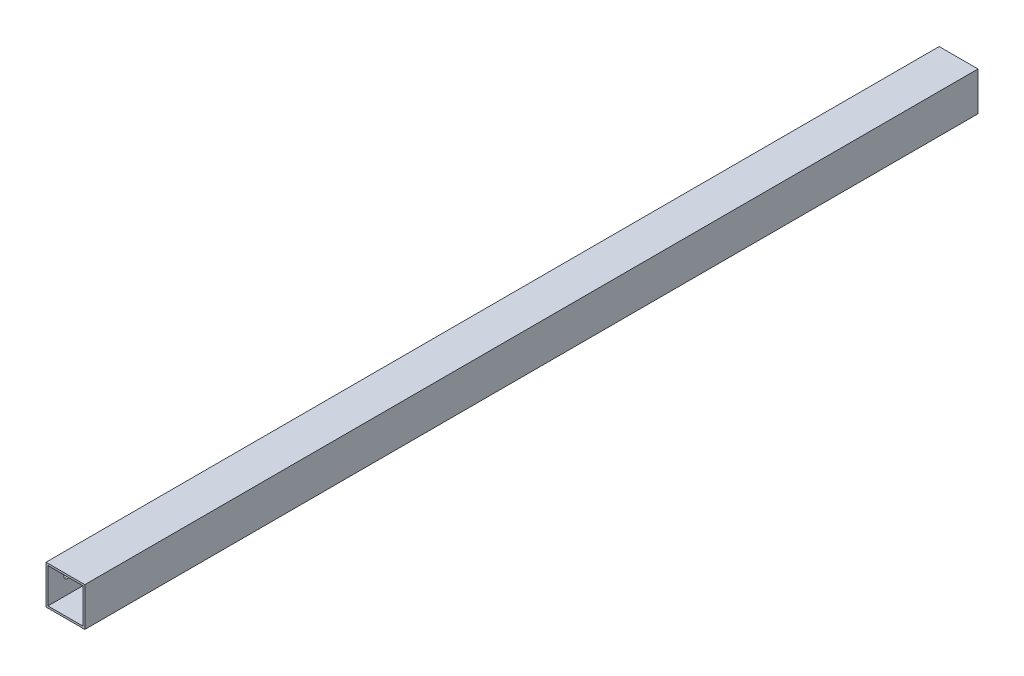
SolidWorks part; units mm, degrees
ref_plane "前视基准面" through (0, 0, 0) normal (0, 0, 1) x (1, 0, 0)
ref_plane "上视基准面" through (0, 0, 0) normal (0, 1, 0) x (1, 0, 0)
ref_plane "右视基准面" through (0, 0, 0) normal (1, 0, 0) x (0, 0, -1)
sketch "草图1" plane through (0, 0, 0) normal (0, 0, 1) x (1, 0, 0)
  line L1 (-10, 10) -> (10, 10)
  line L2 (-10, 10) -> (-10, -10)
  line L3 (-10, -10) -> (10, -10)
  line L4 (10, 10) -> (10, -10)
  line L5 (-10, 10) -> (10, -10) construction
  line L6 (-10, -10) -> (10, 10) construction
  line L7 (-9, 9) -> (9, 9)
  line L8 (-9, 9) -> (-9, -9)
  line L9 (-9, -9) -> (9, -9)
  line L10 (9, 9) -> (9, -9)
  line L11 (-9, 9) -> (9, -9) construction
  line L12 (-9, -9) -> (9, 9) construction
  point P0 (0, 0)
  point P6 (0, 0)
  dimension "D1" = 20
  dimension "D2" = 20
  dimension "D3" = 18
  dimension "D4" = 18
extrude "凸台-拉伸1" add sketch "草图1" along normal blind 460
sketch "草图2" plane through (-10, 0, 0) normal (-1, 0, 0) x (0, 0, 1)
  circle A0 centre (10, 0) radius 1.8
  point P2 (0, 0)
  point P3 (9.4222, 0)
  dimension "D1" = 3.6
extrude "切除-拉伸1" cut sketch "草图2" against normal blind 3
sketch "草图3" plane through (-10, 0, 0) normal (-1, 0, 0) x (0, 0, 1)
  line L1 (0, 10) -> (0, -10) construction
  circle A0 centre (198, 0) radius 1.8
  dimension "D1" = 198
extrude "切除-拉伸2" cut sketch "草图3" against normal blind 3
sketch "草图5" plane through (-10, 0, 0) normal (-1, 0, 0) x (0, 0, 1)
  line L0 (460, 10) -> (460, -10) construction
  circle A0 centre (450, 0) radius 1.8
  point P2 (0, 0)
  dimension "D1" = 10
extrude "切除-拉伸3" cut sketch "草图5" against normal blind 3
sketch "草图6" plane through (-10, 0, 0) normal (-1, 0, 0) x (0, 0, 1)
  line L0 (460, 10) -> (460, -10) construction
  circle A0 centre (262, 0) radius 1.8
  dimension "D1" = 198
extrude "切除-拉伸4" cut sketch "草图6" against normal blind 10
